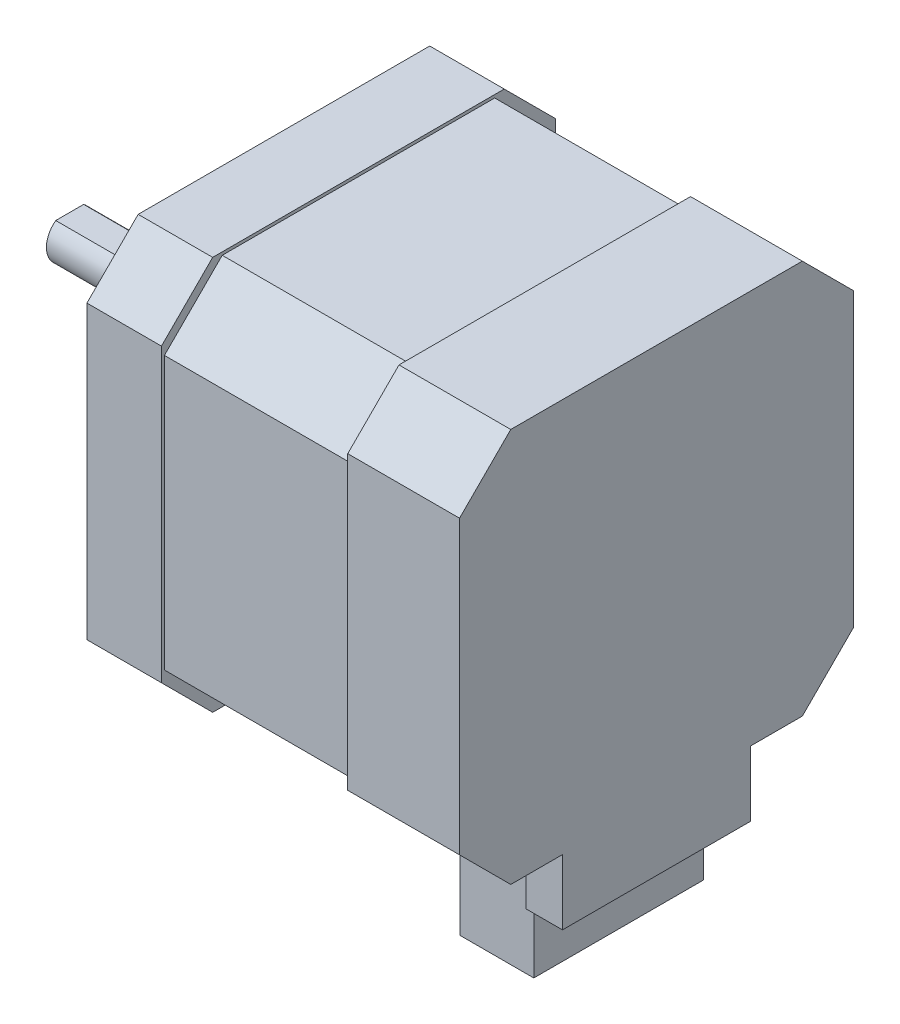
SolidWorks part; units mm, degrees
note: The reader was unsure of these and kept them because the rebuilt part matched: shared geometry of "Sketch1<3>", "Sketch3<3>".
ref_plane "Front Plane" through (0, 0, 0) normal (0, 0, 1) x (1, 0, 0)
ref_plane "Top Plane" through (0, 0, 0) normal (0, 1, 0) x (1, 0, 0)
ref_plane "Right Plane" through (0, 0, 0) normal (1, 0, 0) x (0, 0, -1)
sketch "Sketch1" plane through (0, 0, 0) normal (1, 0, 0) x (0, 0, -1)
  line L0 (0, 0) -> (0, 31.2681) construction
  line L1 (0, 0) -> (45.3119, 0) construction
  line L2 (0, 21.15) -> (15.65, 21.15)
  line L3 (15.65, 21.15) -> (21.15, 15.65)
  line L4 (21.15, 15.65) -> (21.15, 0)
  line L5 (15.65, 21.15) -> (21.15, 21.15) construction
  line L6 (21.15, 21.15) -> (21.15, 15.65) construction
  line L7 (0, 15.5) -> (15.5, 15.5) construction
  line L8 (15.5, 15.5) -> (15.5, 0) construction
  line L9 (21.15, 0) -> (21.15, -15.65)
  line L10 (21.15, -15.65) -> (15.65, -21.15)
  line L11 (15.65, -21.15) -> (0, -21.15)
  line L12 (21.15, -15.65) -> (21.15, -21.15) construction
  line L13 (21.15, -21.15) -> (15.65, -21.15) construction
  line L14 (15.5, 0) -> (15.5, -15.5) construction
  line L15 (15.5, -15.5) -> (0, -15.5) construction
  line L16 (0, -21.15) -> (-15.65, -21.15)
  line L17 (-15.65, -21.15) -> (-21.15, -15.65)
  line L18 (-21.15, -15.65) -> (-21.15, 0)
  line L19 (-15.65, -21.15) -> (-21.15, -21.15) construction
  line L20 (-21.15, -21.15) -> (-21.15, -15.65) construction
  line L21 (0, -15.5) -> (-15.5, -15.5) construction
  line L22 (-15.5, -15.5) -> (-15.5, 0) construction
  line L23 (-21.15, 0) -> (-21.15, 15.65)
  line L24 (-21.15, 15.65) -> (-15.65, 21.15)
  line L25 (-15.65, 21.15) -> (0, 21.15)
  line L26 (-21.15, 15.65) -> (-21.15, 21.15) construction
  line L27 (-21.15, 21.15) -> (-15.65, 21.15) construction
  line L28 (-15.5, 0) -> (-15.5, 15.5) construction
  line L29 (-15.5, 15.5) -> (0, 15.5) construction
  circle A0 centre (15.5, 15.5) radius 1.5
  circle A1 centre (15.5, -15.5) radius 1.5
  circle A2 centre (-15.5, -15.5) radius 1.5
  circle A3 centre (-15.5, 15.5) radius 1.5
  point P11 (0, 0)
  point P43 (0, 0)
  dimension "D3" = 3
  dimension "D1" = 21.15
  dimension "D2" = 15.5
  dimension "D4" = 5.5
  dimension "D5" = 4
extrude "Boss-Extrude1" add sketch "Sketch1" along normal blind 40 contours A0 | A3 | A2 | A1 | L25 L24 L23 L18 L17 L16 L11 L10 L9 L4 L3 L2 A3 A2 A1 A0
extrude "Cut-Extrude1" cut sketch "Sketch1<3>" along normal blind 4 contours A3 | A1 | A2 | A0
sketch "Sketch1<3>" plane through (0, 0, 0) normal (1, 0, 0) x (0, 0, -1) same geometry as "Sketch1"
sketch "Sketch3" plane through (0, 0, 0) normal (-1, 0, 0) x (0, 0, 1)
  circle A0 centre (0, 0) radius 11
  circle A1 centre (0, 0) radius 2.5
  dimension "D1" = 22
  dimension "D2" = 5
extrude "Boss-Extrude2" add sketch "Sketch3" along normal blind 2
extrude "Boss-Extrude3" add sketch "Sketch3<3>" along normal blind 23 contours A1
sketch "Sketch3<3>" plane through (0, 0, 0) normal (-1, 0, 0) x (0, 0, 1) same geometry as "Sketch3"
sketch "Sketch4" plane through (-23, 0, 0) normal (-1, 0, 0) x (0, 0, 1)
  line L0 (-1.5, 2) -> (1.5, 2)
  line L1 (0, 0) -> (0, -2.5) construction
  circle A0 centre (0, 0) radius 2.5 construction
  arc A1 (1.5, 2) -> (-1.5, 2) centre (0, 0) ccw
  arc A2 (-1.5, 2) -> (0, -2.5) centre (0, 0) ccw construction
  arc A3 (0, -2.5) -> (1.5, 2) centre (0, 0) ccw construction
  point P5 (0, -2.5)
  dimension "D1" = 4.5
extrude "Cut-Extrude2" cut sketch "Sketch4" against normal blind 18 contours L0 A1
sketch "Sketch5" plane through (40, 0, 0) normal (1, 0, 0) x (0, 0, -1)
  line L0 (0, 0) -> (0, 21.15) construction
  line L1 (-15.65, 21.15) -> (15.65, 21.15) construction
  line L2 (0, 0) -> (21.15, 0) construction
  line L3 (21.15, 15.65) -> (21.15, -15.65) construction
  line L4 (0, 0) -> (18.4, 18.4) construction
  line L5 (15.65, 21.15) -> (21.15, 15.65) construction
  line L6 (0, 20.8293) -> (14.6255, 20.8293)
  line L7 (14.6255, 20.8293) -> (20.8293, 14.6255)
  line L8 (0, 20.8293) -> (0, 27.5297)
  line L9 (0, 27.5297) -> (27.5297, 27.5297)
  line L10 (18.4, 18.4) -> (27.5297, 27.5297) construction
  line L11 (27.5297, 0) -> (27.5297, 27.5297)
  line L12 (20.8293, 0) -> (27.5297, 0)
  line L13 (20.8293, 0) -> (20.8293, 14.6255)
  line L14 (20.8293, 0) -> (20.8293, -14.6255)
  line L15 (20.8293, -14.6255) -> (14.6255, -20.8293)
  line L16 (20.8293, 0) -> (27.5297, 0)
  line L17 (27.5297, 0) -> (27.5297, -27.5297)
  line L18 (0, -27.5297) -> (27.5297, -27.5297)
  line L19 (0, -20.8293) -> (0, -27.5297)
  line L20 (0, -20.8293) -> (14.6255, -20.8293)
  line L21 (18.4, -18.4) -> (27.5297, -27.5297) construction
  line L22 (0, -20.8293) -> (-14.6255, -20.8293)
  line L23 (-14.6255, -20.8293) -> (-20.8293, -14.6255)
  line L24 (0, -20.8293) -> (0, -27.5297)
  line L25 (0, -27.5297) -> (-27.5297, -27.5297)
  line L26 (-27.5297, 0) -> (-27.5297, -27.5297)
  line L27 (-20.8293, 0) -> (-27.5297, 0)
  line L28 (-20.8293, 0) -> (-20.8293, -14.6255)
  line L29 (-18.4, -18.4) -> (-27.5297, -27.5297) construction
  line L30 (-20.8293, 0) -> (-20.8293, 14.6255)
  line L31 (-20.8293, 14.6255) -> (-14.6255, 20.8293)
  line L32 (-20.8293, 0) -> (-27.5297, 0)
  line L33 (-27.5297, 0) -> (-27.5297, 27.5297)
  line L34 (0, 27.5297) -> (-27.5297, 27.5297)
  line L35 (0, 20.8293) -> (0, 27.5297)
  line L36 (0, 20.8293) -> (-14.6255, 20.8293)
  line L37 (-18.4, 18.4) -> (-27.5297, 27.5297) construction
  point P13 (13.7462, 21.9179)
  point P14 (14.6719, 22.1061)
  point P20 (17.7274, 17.7274)
  point P21 (1.0993, -23.0291)
  point P30 (17.7274, -17.7274)
  point P31 (-20.8293, 14.6255)
  point P39 (-17.7274, -17.7274)
  point P48 (-17.7274, 17.7274)
  point P49 (0, 0)
  point P50 (1.0188, -20.3596)
  point P51 (0.4568, -19.7976)
  dimension "D1" = 4
extrude "Cut-Extrude4" cut sketch "Sketch5" against normal blind 20 from offset 12 contours L33 L34 L35 L36 L31 L30 L32 | L11 L9 L8 L6 L7 L13 L12 | L17 L18 L19 L20 L15 L14 L16 | L25 L26 L27 L28 L23 L22 L24 offset against normal yes
sketch "Sketch6" plane through (0, -21.15, 0) normal (0, -1, 0) x (1, 0, 0)
  line L0 (28, 0) -> (40, 0) construction
  line L1 (28, 15.65) -> (28, -15.65) construction
  line L2 (40, -15.65) -> (40, 15.65) construction
  line L3 (28, -9.1117) -> (28, 9.1117)
  line L4 (28, 9.1117) -> (35.9335, 9.1117)
  line L5 (35.9335, 9.1117) -> (35.9335, -9.1117)
  line L6 (28, -9.1117) -> (35.9335, -9.1117)
  point P10 (35.9335, 0)
  point P11 (35.9335, 0)
extrude "Boss-Extrude4" add sketch "Sketch6" along normal blind 14
sketch "Sketch7" plane through (0, -21.15, 0) normal (0, -1, 0) x (1, 0, 0)
  line L0 (40, -15.65) -> (40, 15.65) construction
  line L1 (40, 10.1002) -> (36.0638, 10.1002)
  line L2 (40, 10.1002) -> (40, -10.1002)
  line L3 (40, -10.1002) -> (36.0638, -10.1002)
  line L4 (36.0638, 10.1002) -> (36.0638, -10.1002)
  line L5 (38.0319, -10.1002) -> (38.0319, -15.65) construction
  line L6 (40, -15.65) -> (28, -15.65) construction
  line L7 (38.0319, 10.1002) -> (38.0319, 15.65) construction
  line L8 (40, 15.65) -> (28, 15.65) construction
extrude "Boss-Extrude5" add sketch "Sketch7" along normal blind 7
